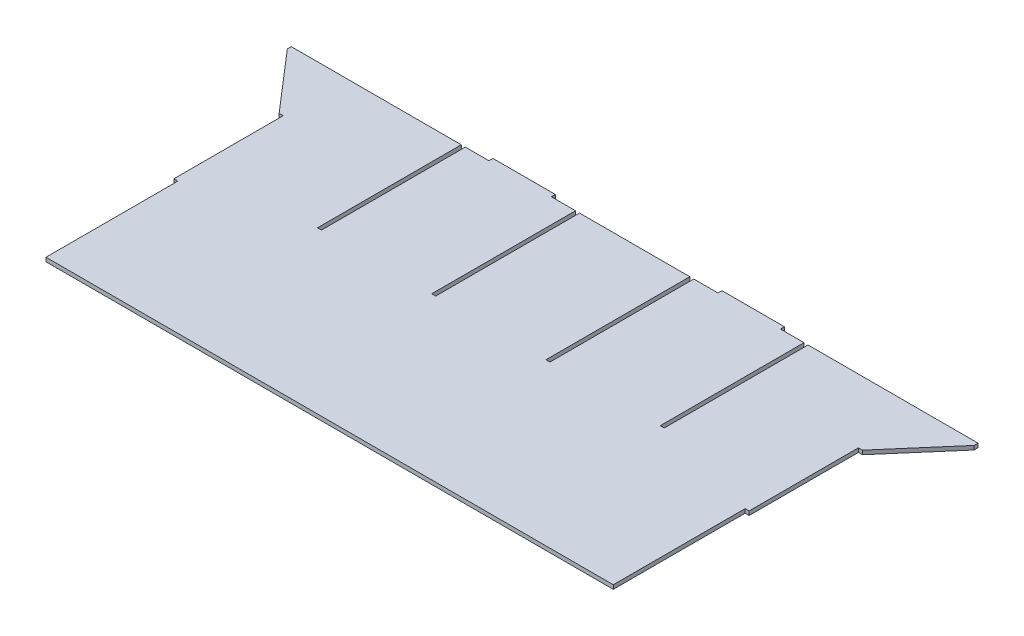
SolidWorks part; units mm, degrees
material "6061-T6 (SS)"
ref_plane "X-Y Datum" through (0, 0, 0) normal (0, 0, 1) x (1, 0, 0)
ref_plane "X-Z Datum" through (0, 0, 0) normal (0, 1, 0) x (1, 0, 0)
ref_plane "Y-Z Datum" through (0, 0, 0) normal (1, 0, 0) x (0, 0, -1)
sketch "Sketch1" plane through (0, 0, 0) normal (0, 0, 1) x (1, 0, 0)
  line L1 (-228.601, -1.5875) -> (228.601, -1.5875)
  line L2 (-228.601, -1.5875) -> (-228.601, 1.5875)
  line L3 (-228.601, 1.5875) -> (228.601, 1.5875)
  line L4 (228.601, -1.5875) -> (228.601, 1.5875)
  line L5 (-228.601, -1.5875) -> (228.601, 1.5875) construction
  line L6 (-228.601, 1.5875) -> (228.601, -1.5875) construction
  point P0 (0, 0)
  dimension "D1" = 3.175
  dimension "D2" = 457.202
extrude "Boss-Extrude1" add sketch "Sketch1" along normal blind 242.425
sketch "Sketch2" plane through (0, 1.5875, 0) normal (0, 1, 0) x (1, 0, 0)
  line L0 (228.601, 0) -> (225.426, 0)
  line L1 (228.601, 0) -> (-228.601, 0) construction
  line L2 (225.426, 0) -> (137.796, 0)
  line L3 (137.796, 0) -> (134.621, 0)
  line L10 (134.621, 0) -> (137.796, 0)
  line L11 (134.621, 0) -> (134.621, -114.3)
  line L12 (134.621, -114.3) -> (137.796, -114.3)
  line L13 (137.796, 0) -> (137.796, -114.3)
  line M2 (228.601, 0) -> (-228.601, 0)
  dimension "D1" = 87.63
  dimension "D2" = 3.175
  dimension "D3" = 114.3
  dimension "D4" = 3.175
extrude "Cut-Extrude1" cut sketch "Sketch2" against normal through all contours L13 L11 L12 M2 region at (136.2085, 1.5875, 57.15)
pattern_linear "LPattern1" count 4 spacing 90.807 along (-1, 0, 0) of "Cut-Extrude1"
sketch "Sketch3" plane through (0, 0, 0) normal (0, 0, -1) x (-1, 0, 0)
  line L1 (-115.8495, 1.5875) -> (-66.1907, 1.5875)
  line L2 (-115.8495, 1.5875) -> (-115.8495, -1.5875)
  line L3 (-115.8495, -1.5875) -> (-66.1907, -1.5875)
  line L4 (-66.1907, 1.5875) -> (-66.1907, -1.5875)
  line L5 (66.1907, 1.5875) -> (115.8495, 1.5875)
  line L6 (66.1907, 1.5875) -> (66.1907, -1.5875)
  line L7 (66.1907, -1.5875) -> (115.8495, -1.5875)
  line L8 (115.8495, 1.5875) -> (115.8495, -1.5875)
extrude "Boss-Extrude2" add sketch "Sketch3" along normal blind 3.175
sketch "Sketch4" plane through (0, -1.5875, 0) normal (0, -1, 0) x (1, 0, 0)
  line L0 (-228.601, 0) -> (-272.876, 0)
  line L2 (-228.601, 242.425) -> (-228.601, 0) construction
  line L3 (-228.601, 50.8) -> (-228.601, 0)
  line L4 (-272.876, 0) -> (-272.876, 3.175)
  line L6 (-228.601, 50.8) -> (-231.776, 50.8)
  line L7 (-231.776, 50.8) -> (-272.876, 3.175)
  dimension "D1" = 44.275
  dimension "D2" = 50.8
  dimension "D3" = 3.175
  dimension "D4" = 3.175
extrude "Boss-Extrude3" add sketch "Sketch4" against normal blind 3.175
mirror "Mirror1" about plane through (0, 0, 0) normal (1, 0, 0) of "Boss-Extrude3"
sketch "Sketch5" plane through (0, -1.5875, 0) normal (0, -1, 0) x (1, 0, 0)
  line L1 (-228.601, 242.425) -> (-225.426, 242.425)
  line L2 (-228.601, 242.425) -> (-228.601, 137.65)
  line L3 (-228.601, 137.65) -> (-225.426, 137.65)
  line L4 (-225.426, 242.425) -> (-225.426, 137.65)
  dimension "D1" = 3.175
  dimension "D2" = 104.775
extrude "Cut-Extrude2" cut sketch "Sketch5" against normal blind 3.175
mirror "Mirror2" about plane through (0, 0, 0) normal (1, 0, 0) of "Cut-Extrude2"
